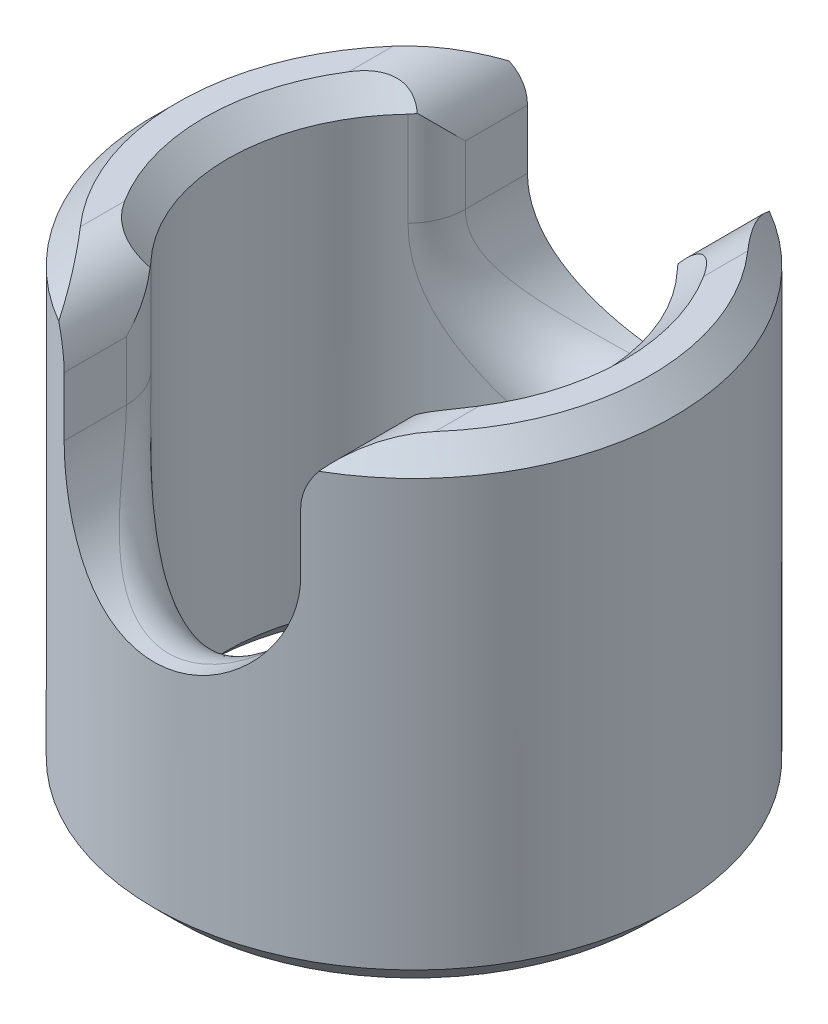
SolidWorks part; units mm, degrees
material "6061 Alloy"
ref_plane "Front Plane" through (0, 0, 0) normal (0, 0, 1) x (1, 0, 0)
ref_plane "Top Plane" through (0, 0, 0) normal (0, 1, 0) x (1, 0, 0)
ref_plane "Right Plane" through (0, 0, 0) normal (1, 0, 0) x (0, 0, -1)
sketch "Sketch1" plane through (0, 0, 0) normal (0, 1, 0) x (1, 0, 0)
  circle A0 centre (0, 0) radius 11.175
  circle A1 centre (0, 0) radius 8
  dimension "D1" = 16
  dimension "D2" = 22.35
extrude "Boss-Extrude1" add sketch "Sketch1" along normal blind 20.32
chamfer "Chamfer1" distance 1.016 angle 45 4 edges at (0, 20.32, 8) (0, 20.32, 11.175) (0, 0, 11.175) (0, 0, 8)
sketch "Sketch2" plane through (0, 0, 0) normal (0, 0, 1) x (1, 0, 0)
  line L0 (5.08, 20.32) -> (5.08, 15.24)
  line L3 (10.159, 20.32) -> (-10.159, 20.32) construction
  line L4 (10.159, 20.32) -> (-10.159, 20.32)
  line L5 (-5.08, 15.24) -> (-5.08, 20.32)
  arc A0 (5.08, 15.24) -> (-5.08, 15.24) centre (0, 15.24) cw
  point P11 (0, 20.32)
  dimension "D3" = 5.08
  dimension "D2" = 5.08
extrude "Cut-Extrude1" cut sketch "Sketch2" against normal through all and the other way through all contours A0 L0 L5 region at (0, 15.7142, 0)
fillet "Fillet1" radius 2.54 10 edges at (-5.08, 17.272, 6.1801) (5.08, 17.272, 6.1801) (5.08, 17.272, -6.1801) (-5.08, 17.272, -6.1801) (0.1377, 10.1619, 7.9988) (-0.1377, 10.1619, -7.9988) (-5.08, 20.32, 8.1231) (5.08, 20.32, 8.1231) (-5.08, 20.32, -8.1231) (5.08, 20.32, -8.1231)
